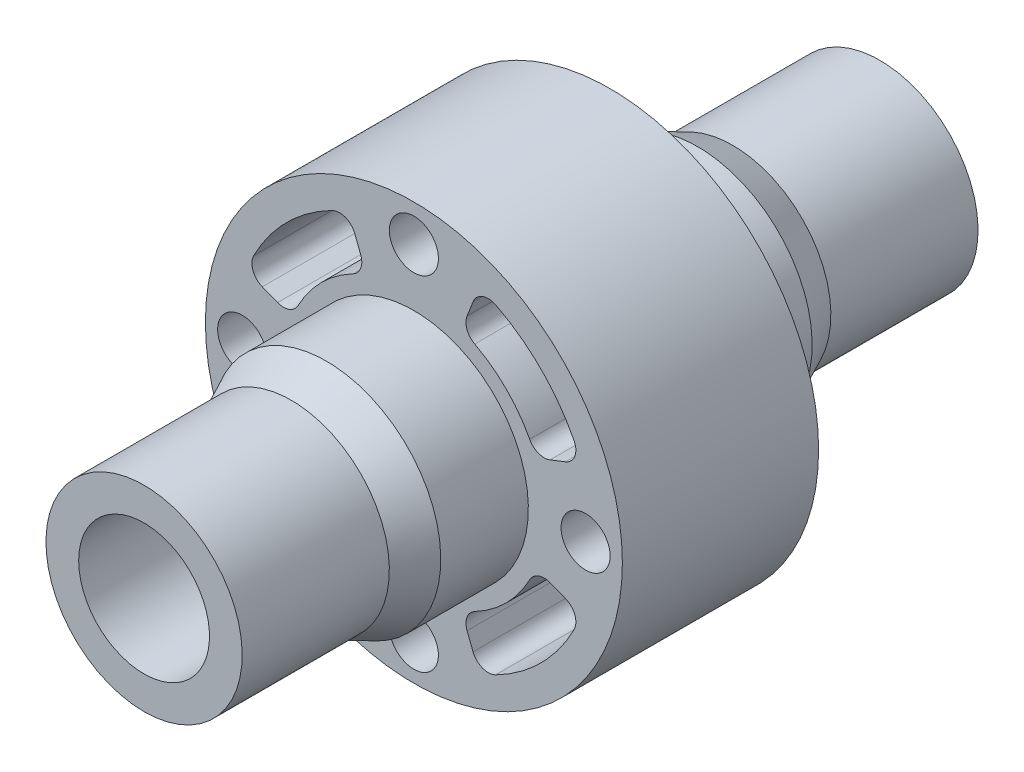
SolidWorks part; units mm, degrees
ref_plane "前视基准面" through (0, 0, 0) normal (0, 0, 1) x (1, 0, 0)
ref_plane "上视基准面" through (0, 0, 0) normal (0, 1, 0) x (1, 0, 0)
ref_plane "右视基准面" through (0, 0, 0) normal (1, 0, 0) x (0, 0, -1)
sketch "草图1" plane through (0, 0, 0) normal (1, 0, 0) x (0, 0, -1)
  line L0 (-21.2214, 0) -> (28.1258, 0) construction
  line L1 (-22.5, 0) -> (-22.5, 6)
  line L2 (-22.5, 6) -> (-13.5, 6)
  line L3 (-13.5, 6) -> (-13.5, 7) construction
  line L4 (-11.3555, 7) -> (-6, 7)
  line L5 (-6, 7) -> (-6, 14)
  line L6 (-6, 14) -> (6, 14)
  line L7 (0, 14) -> (0, 0) construction
  line L8 (6, 7) -> (6, 14)
  line L9 (11.3555, 7) -> (6, 7)
  line L10 (13.5, 6) -> (13.5, 7) construction
  line L11 (22.5, 6) -> (13.5, 6)
  line L12 (22.5, 0) -> (22.5, 6)
  line L13 (-22.5, 0) -> (22.5, 0)
  line L14 (-13.5, 6) -> (-11.3555, 7)
  line L15 (-13.5, 7) -> (-11.3555, 7) construction
  line L16 (13.5, 6) -> (11.3555, 7)
  line L17 (13.5, 7) -> (11.3555, 7) construction
  dimension "D1" = 6
  dimension "D2" = 12
  dimension "D3" = 14
  dimension "D4" = 9
  dimension "D5" = 7.5
  dimension "D6" = 7
  dimension "D7" = 45
  dimension "D8" = 25
revolve "旋转1" add sketch "草图1" angle 360 about L13
sketch "草图2" plane through (0, 0, 6) normal (0, 0, 1) x (1, 0, 0)
  line L0 (0, 0) -> (0, 10.5) construction
  circle A0 centre (0, 0) radius 10.5 construction
  circle A1 centre (0, 10.5) radius 1.5
  circle A2 centre (0, 0) radius 10.5 construction
  circle A3 centre (10.5, 0) radius 1.5
  circle A4 centre (0, 0) radius 10.5 construction
  circle A5 centre (0, -10.5) radius 1.5
  circle A6 centre (0, 0) radius 10.5 construction
  circle A7 centre (-10.5, 0) radius 1.5
  dimension "D1" = 21
  dimension "D2" = 3
  dimension "D3" = 4
extrude "切除-拉伸1" cut sketch "草图2" against normal through all
sketch "草图4" plane through (0, 0, -6) normal (0, 0, -1) x (-1, 0, 0)
  circle A0 centre (0, 0) radius 12.75
  circle A1 centre (0, 0) radius 14 construction
  circle A2 centre (0, 0) radius 14
  dimension "D1" = 25.5
extrude "切除-拉伸4" cut sketch "草图4" against normal through all
sketch "草图5" plane through (0, 0, -6) normal (0, 0, -1) x (-1, 0, 0)
  line L0 (-9.2687, 3.6181) -> (-8.332, 3.2525)
  line L1 (-3.6181, 9.2687) -> (-3.2525, 8.332)
  line L8 (3.6181, 9.2687) -> (3.2525, 8.332)
  line L9 (9.2687, 3.6181) -> (8.332, 3.2525)
  line L10 (9.2687, -3.6181) -> (8.332, -3.2525)
  line L11 (3.6181, -9.2687) -> (3.2525, -8.332)
  line L12 (-3.6181, -9.2687) -> (-3.2525, -8.332)
  line L13 (-9.2687, -3.6181) -> (-8.332, -3.2525)
  circle A2 centre (-10.5, 0) radius 1.5 construction
  circle A4 centre (0, 10.5) radius 1.5 construction
  arc A6 (-3.7191, 7.083) -> (-7.083, 3.7191) centre (0, 0) ccw
  arc A7 (-5.0046, 9.7956) -> (-9.7956, 5.0046) centre (0, 0) ccw
  arc A14 (-8.332, 3.2525) -> (-7.083, 3.7191) centre (-7.9683, 4.184) ccw
  arc A15 (-9.2687, 3.6181) -> (-9.7956, 5.0046) centre (-8.9051, 4.5497) cw
  arc A16 (-3.2525, 8.332) -> (-3.7191, 7.083) centre (-4.184, 7.9683) cw
  arc A17 (-3.6181, 9.2687) -> (-5.0046, 9.7956) centre (-4.5497, 8.9051) ccw
  arc A18 (3.6181, 9.2687) -> (5.0046, 9.7956) centre (4.5497, 8.9051) cw
  arc A19 (3.2525, 8.332) -> (3.7191, 7.083) centre (4.184, 7.9683) ccw
  arc A20 (7.083, 3.7191) -> (3.7191, 7.083) centre (0, 0) ccw
  arc A21 (8.332, 3.2525) -> (7.083, 3.7191) centre (7.9683, 4.184) cw
  arc A22 (9.2687, 3.6181) -> (9.7956, 5.0046) centre (8.9051, 4.5497) ccw
  arc A23 (9.7956, 5.0046) -> (5.0046, 9.7956) centre (0, 0) ccw
  arc A24 (9.2687, -3.6181) -> (9.7956, -5.0046) centre (8.9051, -4.5497) cw
  arc A25 (8.332, -3.2525) -> (7.083, -3.7191) centre (7.9683, -4.184) ccw
  arc A26 (3.7191, -7.083) -> (7.083, -3.7191) centre (0, 0) ccw
  arc A27 (3.2525, -8.332) -> (3.7191, -7.083) centre (4.184, -7.9683) cw
  arc A28 (3.6181, -9.2687) -> (5.0046, -9.7956) centre (4.5497, -8.9051) ccw
  arc A29 (5.0046, -9.7956) -> (9.7956, -5.0046) centre (0, 0) ccw
  arc A30 (-3.6181, -9.2687) -> (-5.0046, -9.7956) centre (-4.5497, -8.9051) cw
  arc A31 (-3.2525, -8.332) -> (-3.7191, -7.083) centre (-4.184, -7.9683) ccw
  arc A32 (-7.083, -3.7191) -> (-3.7191, -7.083) centre (0, 0) ccw
  arc A33 (-8.332, -3.2525) -> (-7.083, -3.7191) centre (-7.9683, -4.184) cw
  arc A34 (-9.2687, -3.6181) -> (-9.7956, -5.0046) centre (-8.9051, -4.5497) ccw
  arc A35 (-9.7956, -5.0046) -> (-5.0046, -9.7956) centre (0, 0) ccw
  point P23 (0, 0)
  point P25 (0, 0)
  point P27 (-10.247, 4)
  point P32 (-4, 10.247)
  point P44 (0, 0)
  point P57 (0, 0)
  point P63 (0, 0)
  dimension "D3" = 11
  dimension "D4" = 8
  dimension "D6" = 1
  dimension "D1" = 4
  dimension "D2" = 4
extrude "切除-拉伸5" cut sketch "草图5" against normal through all
sketch "草图6" plane through (0, 0, -22.5) normal (0, 0, -1) x (-1, 0, 0)
  circle A0 centre (0, 0) radius 4
  dimension "D1" = 8
extrude "切除-拉伸6" cut sketch "草图6" against normal through all
move or copy body "实体-移动/复制1" [suppressed] bodies to move or copy 113
